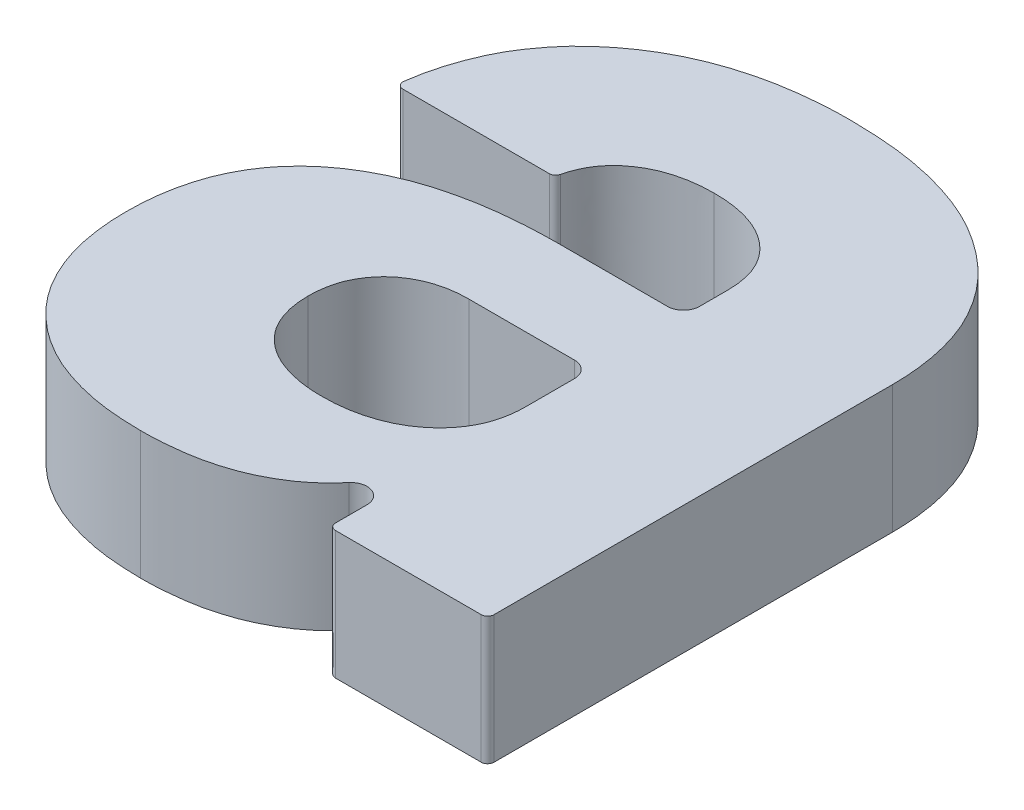
SolidWorks part; units mm, degrees
ref_plane "Front Plane" through (0, 0, 0) normal (0, 0, 1) x (1, 0, 0)
ref_plane "Top Plane" through (0, 0, 0) normal (0, 1, 0) x (1, 0, 0)
ref_plane "Right Plane" through (0, 0, 0) normal (1, 0, 0) x (0, 0, -1)
sketch "Sketch1" plane through (0, 0, 0) normal (0, 1, 0) x (1, 0, 0)
  line L0 (46.5715, 56.3317) -> (66.092, 56.3317)
  line L1 (66.092, 56.3317) -> (66.092, 63.3423)
  line L2 (37.1581, 65.0763) -> (12.3365, 65.0763)
  line L3 (91.7806, 63.3423) -> (91.7806, 0)
  line L4 (91.7806, 0) -> (66.9589, 0)
  line L5 (66.9589, 0) -> (66.9589, 15.4083)
  line L8 (66.092, 31.6835) -> (66.092, 41.7905)
  line L9 (66.092, 41.7905) -> (47.0918, 41.7905)
  line L10 (66.9589, 15.3163) -> (66.9589, 18.3373)
  spline S0 degree 3 poles (39.2142, -1.7093) (36.9649, -1.6836) (33.6472, -1.5277) (29.4144, -0.6716) (26.4979, 0.1734) (23.7457, 1.2286) (21.1988, 2.578) (18.8195, 4.1379) (16.6706, 5.9622) (14.7081, 7.9522) (13.0114, 10.1477) (11.5929, 12.5228) (10.4257, 15.0651) (9.5006, 17.777) (8.6411, 21.7134) (8.3761, 24.7856) (8.3977, 26.8777) knots 0 0 0 0 0.142196 0.208635 0.272136 0.333692 0.394305 0.453716 0.512907 0.571877 0.629839 0.687581 0.746114 0.806108 0.868066 1 1 1 1
  spline S1 degree 3 poles (8.3977, 26.8777) (8.3818, 29.12) (8.6769, 32.415) (9.7172, 36.5904) (10.7834, 39.4497) (12.1871, 42.0875) (13.8721, 44.5417) (15.9083, 46.752) (18.2199, 48.7717) (20.8388, 50.5518) (23.7179, 52.1122) (26.8693, 53.4373) (30.2945, 54.4804) (33.9836, 55.3339) (39.4249, 56.1311) (43.6688, 56.3182) (46.5715, 56.3317) knots 0 0 0 0 0.122914 0.18034 0.235499 0.289773 0.343774 0.398255 0.454089 0.511727 0.571487 0.633371 0.698809 0.767557 0.840803 1 1 1 1
  spline S2 degree 3 poles (66.092, 63.3423) (66.0852, 65.0173) (65.6716, 67.5381) (63.9773, 70.3991) (62.2621, 72.1697) (60.1539, 73.5957) (56.7187, 75.0027) (53.8439, 75.3504) (51.8728, 75.3319) knots 0 0 0 0 0.241147 0.355168 0.471467 0.591556 0.717225 1 1 1 1
  spline S3 degree 3 poles (51.8728, 75.3319) (50.0273, 75.3466) (47.3448, 75.0239) (44.0319, 73.8792) (41.9345, 72.6531) (40.1152, 71.1757) (38.2141, 68.7618) (37.4283, 66.5755) (37.1581, 65.0763) knots 0 0 0 0 0.282231 0.409765 0.533776 0.652238 0.766534 1 1 1 1
  spline S4 degree 3 poles (12.3365, 65.0763) (12.5553, 67.3613) (13.235, 70.6971) (14.7677, 74.8925) (16.1282, 77.8342) (17.8822, 80.544) (19.8534, 83.1133) (22.1516, 85.4768) (24.7387, 87.6231) (27.5425, 89.5739) (30.5712, 91.2716) (33.7886, 92.7059) (37.2077, 93.8679) (40.8085, 94.7916) (45.9924, 95.6502) (50.0065, 95.9108) (52.7398, 95.8928) knots 0 0 0 0 0.122517 0.180678 0.238267 0.295145 0.352648 0.410956 0.470739 0.531892 0.593089 0.655853 0.719713 0.785693 0.854119 1 1 1 1
  spline S5 degree 3 poles (52.7398, 95.8928) (55.5842, 95.8593) (59.7678, 95.6699) (65.1339, 94.714) (68.8338, 93.7589) (72.2979, 92.5113) (75.5403, 91.0119) (78.5179, 89.1795) (81.2801, 87.1339) (83.7454, 84.8393) (85.9128, 82.34) (87.7072, 79.6302) (89.2322, 76.7555) (90.355, 73.6657) (91.4777, 69.2153) (91.7709, 65.7152) (91.7806, 63.3423) knots 0 0 0 0 0.149033 0.218376 0.284935 0.348771 0.410828 0.471527 0.531423 0.590437 0.647435 0.704127 0.760181 0.817336 0.875715 1 1 1 1
  spline S6 degree 3 poles (66.9589, 18.3373) (66.7999, 16.8841) (66.3603, 14.6705) (65.27, 11.8611) (64.1956, 9.8048) (62.8793, 7.8859) (61.2969, 6.1253) (59.5198, 4.4905) (57.5359, 3.0261) (55.3657, 1.7727) (53.0649, 0.6644) (50.5884, -0.1838) (47.9793, -0.9) (44.1747, -1.5078) (41.2287, -1.7244) (39.2142, -1.7093) knots 0 0 0 0 0.116227 0.17812 0.238865 0.300193 0.362467 0.426547 0.491762 0.557924 0.625422 0.694312 0.765606 0.840135 1 1 1 1
  spline S7 degree 3 poles (48.801, 17.1175) (51.1234, 17.0876) (54.5205, 17.5752) (58.6449, 19.2659) (61.2537, 21.0327) (63.3989, 23.2068) (65.5518, 26.632) (66.1075, 29.672) (66.092, 31.6835) knots 0 0 0 0 0.274902 0.401207 0.525237 0.645639 0.760773 1 1 1 1
  spline S8 degree 3 poles (47.0918, 41.7905) (45.3057, 41.819) (42.6785, 41.4365) (39.5688, 39.9768) (37.6034, 38.5257) (36.0382, 36.6926) (34.4161, 33.8263) (34.0754, 31.2988) (34.0616, 29.6274) knots 0 0 0 0 0.267691 0.38933 0.5112 0.630383 0.747673 1 1 1 1
  spline S9 degree 3 poles (34.0616, 29.6274) (34.0499, 27.8561) (34.4947, 25.2338) (36.1959, 22.2123) (37.9636, 20.3751) (40.1487, 18.8947) (43.7413, 17.4605) (46.7353, 17.0819) (48.801, 17.1175) knots 0 0 0 0 0.243842 0.356155 0.471739 0.591018 0.716186 1 1 1 1
  point P1 (66.959, 18.3186)
  point P90 (66.9589, 18.3071)
extrude "Boss-Extrude1" add sketch "Sketch1" against normal blind 20 contours S6 L10 L5 L4 L3 S5 S4 L2 S3 S2 L1 L0 S1 S0 S9 S8 L9 L8 S7 region at (53.7364, 0, -44.9409)
fillet "Fillet1" radius 2.5 3 edges at (66.092, -10, -56.3317) (66.092, -10, -41.7905) (66.9589, -10, -18.3373)
fillet "Fillet2" radius 1 4 edges at (91.7806, -10, 0) (66.9589, -10, 0) (12.3365, -10, -65.0763) (37.1581, -10, -65.0763)
